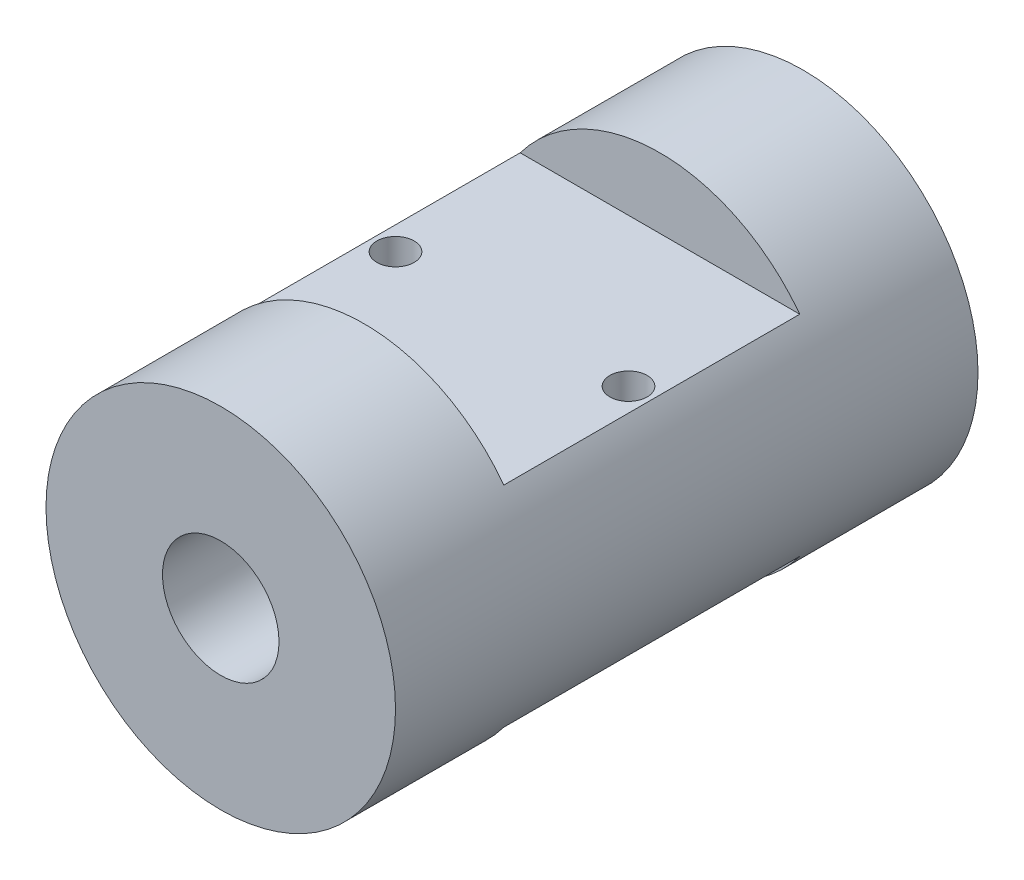
SolidWorks part; units mm, degrees
material "Delrin 2700 NC010, Low Viscosity Acetal Copolymer (SS)"
ref_plane "Front Plane" through (0, 0, 0) normal (0, 0, 1) x (1, 0, 0)
ref_plane "Top Plane" through (0, 0, 0) normal (0, 1, 0) x (1, 0, 0)
ref_plane "Right Plane" through (0, 0, 0) normal (1, 0, 0) x (0, 0, -1)
sketch "Sketch1" plane through (0, 0, 0) normal (0, 1, 0) x (1, 0, 0)
  line L0 (0, -25) -> (0, 25) construction
  line L1 (15, -25) -> (5, -25)
  line L2 (15, -25) -> (15, 25)
  line L3 (15, 25) -> (5, 25)
  line L4 (5, -25) -> (5, 25)
  line L5 (0, 25) -> (5, 25) construction
  line L6 (5, -25) -> (0, -25) construction
  line L7 (0, 0) -> (5, 0) construction
  dimension "D1" = 10
  dimension "D2" = 30
  dimension "D3" = 50
revolve "Revolve1" add sketch "Sketch1" angle 360 about L0
cosmetic thread "Cosmetic Thread1" parameters "D2"=12
sketch "Sketch2" plane through (0, 0, 0) normal (0, 0, 1) x (1, 0, 0)
  line L0 (-13.4075, 0) -> (27.2995, 0) construction
  line L1 (-15, 15) -> (15, 15)
  line L2 (-15, 15) -> (-15, 9)
  line L3 (-15, 9) -> (15, 9)
  line L4 (15, 15) -> (15, 9)
  line L5 (-15, -15) -> (15, -15)
  line L6 (-15, -15) -> (-15, -9)
  line L7 (-15, -9) -> (15, -9)
  line L8 (15, -15) -> (15, -9)
  line L9 (-6, 9) -> (-6, -9) construction
  line L10 (6, 9) -> (6, -9) construction
  line L11 (0, 0) -> (0, 9) construction
  line L12 (8.2995, 9) -> (8.2995, -9) construction
  line L13 (11.2995, -9) -> (11.2995, 9) construction
  circle A0 centre (0, 0) radius 15 construction
  dimension "D1" = 12
  dimension "D2" = 3
  dimension "D3" = 18
extrude "Cut-Extrude1" cut sketch "Sketch2" against normal blind 12.7 and the other way blind 12.7
sketch "Sketch3" plane through (0, 0, 0) normal (0, 0, 1) x (1, 0, 0)
  line L0 (10, -9) -> (10, -19.0464) construction
  line L1 (10, 9) -> (8.4, 9)
  line L2 (10, 9) -> (10, -9)
  line L3 (10, -9) -> (8.4, -9)
  line L4 (8.4, 9) -> (8.4, -9)
  line L5 (-10, -9) -> (-10, -14.3538) construction
  line L6 (-10, 9) -> (-8.4, 9)
  line L7 (-10, 9) -> (-10, -9)
  line L8 (-10, -9) -> (-8.4, -9)
  line L9 (-8.4, 9) -> (-8.4, -9)
  line L10 (0, 0) -> (0, 11.1925) construction
  line L11 (0, 0) -> (20.8751, 0) construction
  line L12 (-12, 9) -> (12, 9) construction
  line L13 (12, -9) -> (-12, -9) construction
  line L14 (10, 9) -> (11.6, 9) construction
  line L15 (11.6, 9) -> (11.6, -9) construction
  line L16 (11.6, -9) -> (10, -9) construction
  line L17 (-10, -9) -> (-11.6, -9) construction
  line L18 (-11.6, -9) -> (-11.6, 9) construction
  line L19 (-11.6, 9) -> (-10, 9) construction
  dimension "D1" = 20
  dimension "D2" = 3.2
revolve "Cut-Revolve1" cut sketch "Sketch3" angle 360 about L0
revolve "Cut-Revolve2" cut sketch "Sketch3<3>" angle 360 about L5
sketch "Sketch3<3>" plane through (0, 0, 0) normal (0, 0, 1) x (1, 0, 0) same geometry as "Sketch3"
